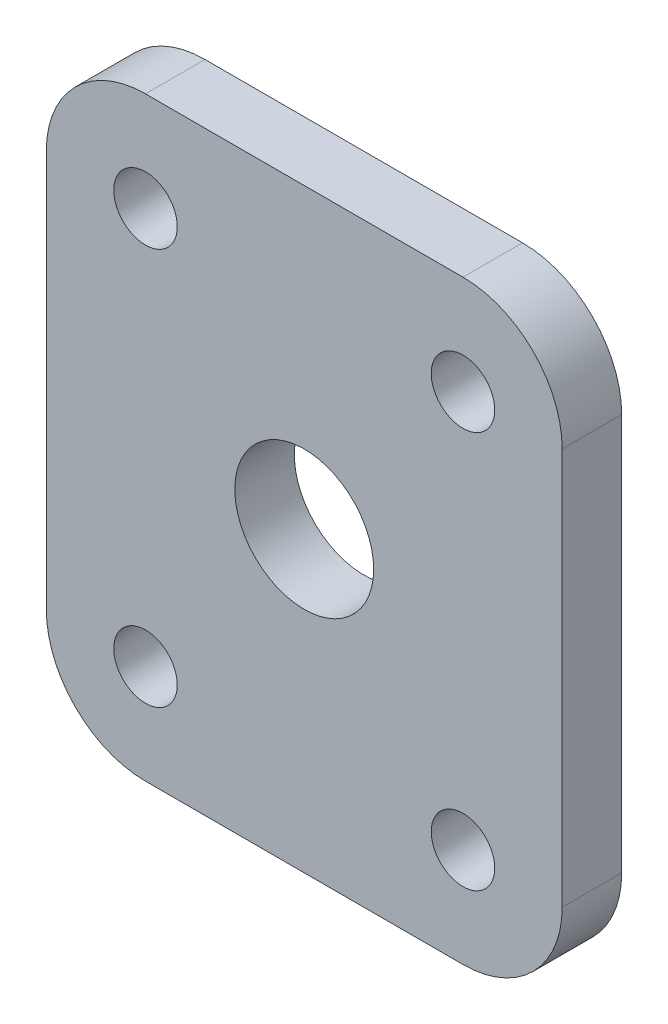
SolidWorks part; units mm, degrees
ref_plane "Plano frontal" through (0, 0, 0) normal (0, 0, 1) x (1, 0, 0)
ref_plane "Plano superior" through (0, 0, 0) normal (0, 1, 0) x (1, 0, 0)
ref_plane "Plano direito" through (0, 0, 0) normal (1, 0, 0) x (0, 0, -1)
sketch "Esboço1" plane through (0, 0, 0) normal (0, 0, 1) x (1, 0, 0)
  line L1 (-13, -15) -> (13, -15)
  line L2 (-13, -15) -> (-13, 15)
  line L3 (-13, 15) -> (13, 15)
  line L4 (13, -15) -> (13, 15)
  line L5 (0, 15) -> (0, -15) construction
  line L6 (-13, 0) -> (13, 0) construction
  circle A0 centre (-8, 10) radius 1.6
  circle A2 centre (8, 10) radius 1.6
  circle A3 centre (8, -10) radius 1.6
  circle A4 centre (-8, -10) radius 1.6
  circle A5 centre (0, 0) radius 3.5
  point P0 (0, 0)
  dimension "D1" = 16
  dimension "D2" = 20
  dimension "D3" = 5
  dimension "D5" = 3.2
  dimension "D6" = 7
  dimension "D4" = 5
extrude "Ressalto-extrusão1" add sketch "Esboço1" along normal blind 3 contours L1 L4 L3 L2 A5 A2 A0 A3 A4 region at (-12.603, 0, 0)
fillet "Filete1" radius 5 4 edges at (-13, -15, 1.5) (13, -15, 1.5) (-13, 15, 1.5) (13, 15, 1.5)
